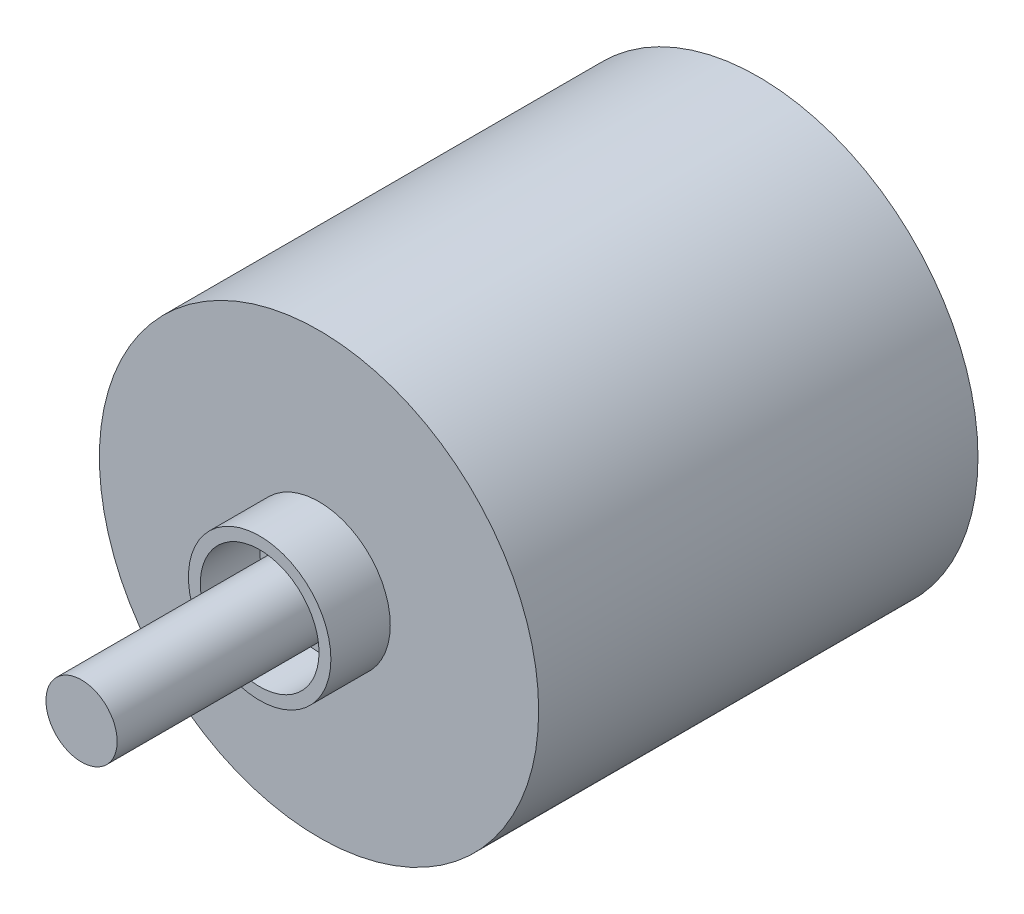
SolidWorks part; units mm, degrees
ref_plane "Alzado" through (0, 0, 0) normal (0, 0, 1) x (1, 0, 0)
ref_plane "Planta" through (0, 0, 0) normal (0, 1, 0) x (1, 0, 0)
ref_plane "Vista lateral" through (0, 0, 0) normal (1, 0, 0) x (0, 0, -1)
sketch "Croquis1" plane through (0, 0, 0) normal (0, 0, 1) x (1, 0, 0)
  circle A0 centre (0, 0) radius 18.5
  circle A1 centre (0, 0) radius 15.5 construction
  dimension "D1" = 37
  dimension "D2" = 31
extrude "Saliente-Extruir1" add sketch "Croquis1" along normal blind 37
sketch "Croquis2" plane through (0, 0, 37) normal (0, 0, 1) x (1, 0, 0)
  circle A0 centre (0, 0) radius 6
  circle A1 centre (0, 0) radius 3
  circle A2 centre (0, 0) radius 5
  dimension "D1" = 12
  dimension "D2" = 1
  dimension "D3" = 6
extrude "Saliente-Extruir2" add sketch "Croquis2" along normal blind 5 contours A0 A2 region at (-5.8303, 0, 37)
extrude "Saliente-Extruir3" add sketch "Croquis2<3>" along normal blind 20 contours A1 region at (0, 0, 37)
sketch "Croquis2<3>" plane through (0, 0, 37) normal (0, 0, 1) x (1, 0, 0) same geometry as "Croquis2"
hole_wizard "Taladro de margen para M31" positions "Croquis3" profile "Croquis5" hole size "M3" standard "Ansi Metric"
sketch "Croquis3" plane through (0, 0, 0) normal (0, 0, -1) x (-1, 0, 0)
  line L0 (0, 0) -> (0, 15.5) construction
  circle A0 centre (0, 0) radius 15.5
  point P0 (0, 15.5)
  point P16 (13.4234, 7.75)
  point P17 (13.4234, -7.75)
  point P18 (0, -15.5)
  point P19 (-13.4234, -7.75)
  point P20 (-13.4234, 7.75)
  dimension "D1" = 31
  dimension "D3" = 15.5
  dimension "D2" = 6
sketch "Croquis5" plane through (0, 15.5, 0) normal (1, 0, 0) x (0, 1, 0)
  line L0 (0, 0) -> (0, 5)
  line L1 (0, 5) -> (1.7, 5)
  line L2 (1.7, 5) -> (1.7, 0)
  line L5 (1.7, 0) -> (0, 0)
  line L10 (0, 5) -> (-1.7, 5) construction
  line L11 (0, -6.35) -> (0, 107.95) construction
  dimension "Diámetro de taladro" = 3.4
  dimension "Profundidad de taladro" = 5
  dimension "Ángulo de perforador" = 180
